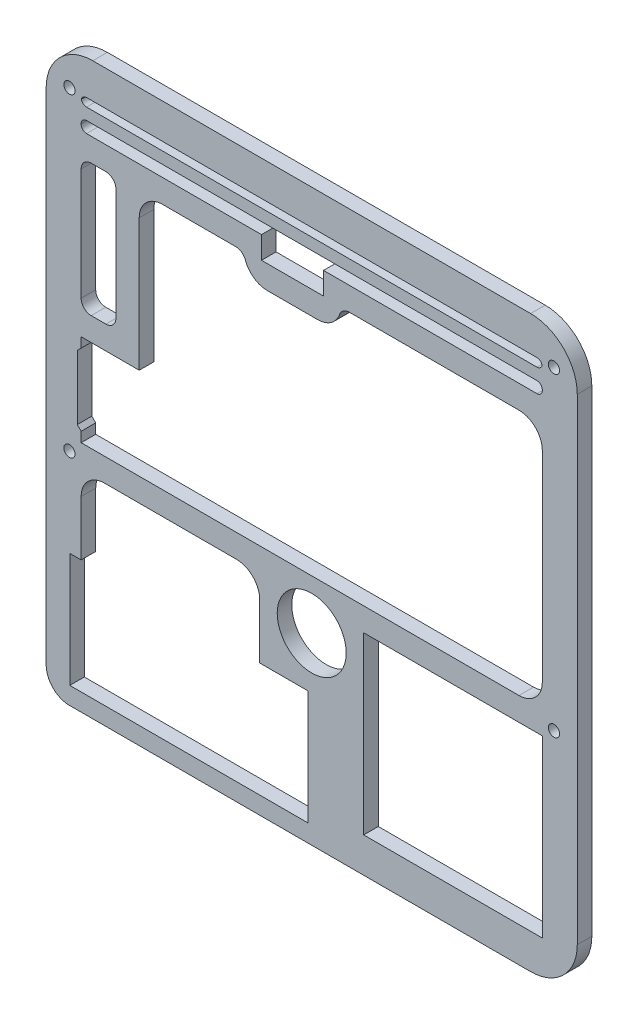
SolidWorks part; units mm, degrees
ref_plane "Front Plane" through (0, 0, 0) normal (0, 0, 1) x (1, 0, 0)
ref_plane "Top Plane" through (0, 0, 0) normal (0, 1, 0) x (1, 0, 0)
ref_plane "Right Plane" through (0, 0, 0) normal (1, 0, 0) x (0, 0, -1)
sketch "Sketch1" plane through (0, 0, 0) normal (0, 0, 1) x (1, 0, 0)
  line L0 (63.9883, 52.5442) -> (63.9883, 48.7342) construction
  line L1 (6.1648, -9.556) -> (64.0322, -9.556)
  line L2 (6.1648, -9.556) -> (6.1648, 52.5442)
  line L3 (6.1648, 52.5442) -> (64.0322, 52.5442)
  line L4 (64.0322, -9.556) -> (64.0322, 52.5442)
  line L5 (60.2222, 48.7342) -> (9.9748, 48.7342)
  line L6 (60.2222, 48.7342) -> (60.2222, -5.746)
  line L7 (60.2222, -5.746) -> (9.9748, -5.746)
  line L8 (9.9748, 48.7342) -> (9.9748, -5.746)
  line L9 (63.9883, 50.6392) -> (18.0707, 50.6392) construction
  line L10 (9.9748, 39.3805) -> (6.1648, 39.3805) construction
  line L11 (8.0698, 39.3805) -> (8.0698, 23.9527) construction
  line L12 (13.5248, -5.746) -> (13.5248, -9.556) construction
  line L13 (13.5248, -7.651) -> (21.1598, -7.651) construction
  line L14 (64.0322, 38.1916) -> (60.2222, 38.1916) construction
  line L15 (62.1272, 38.1916) -> (62.1272, 22.3321) construction
  line L16 (48.6748, 50.6392) -> (23.5288, 50.6392) construction
  line L17 (62.1272, 27.1202) -> (62.1272, 39.363) construction
  line L18 (8.0698, 15.868) -> (8.0698, 3.6252) construction
  line L19 (35.2238, -7.651) -> (34.6952, -7.651) construction
  dimension "D1" = 3.81
  dimension "D2" = 3.81
extrude "Boss-Extrude1" add sketch "Sketch1" along normal blind 1.5875
sketch "Sketch2" plane through (0, 0, 0) normal (0, 0, -1) x (-1, 0, 0)
  line L0 (-60.2222, -5.746) -> (-60.2222, 48.7342) construction
  line L1 (-60.2222, 15.868) -> (-9.9748, 15.868)
  line L2 (-60.2222, 15.868) -> (-60.2222, 13.328)
  line L3 (-60.2222, 13.328) -> (-9.9748, 13.328)
  line L4 (-9.9748, 15.868) -> (-9.9748, 13.328)
  line L5 (-9.9748, 48.7342) -> (-9.9748, -5.746) construction
  line L6 (-13.0532, 15.868) -> (-50.7532, 15.868) construction
  line L7 (-36.3812, 45.3306) -> (-36.3812, 43.2224) construction
  line L8 (-29.6248, 43.2224) -> (-29.6248, 45.3306) construction
  line L9 (-25.4592, 42.9049) -> (-46.8968, 42.9049) construction
  line L11 (-60.2222, 45.3306) -> (-36.3812, 45.3306)
  line L12 (-60.2222, 45.3306) -> (-60.2222, 42.7906)
  line L13 (-60.2222, 42.7906) -> (-38.2862, 42.7906)
  line L14 (-9.9748, 45.3306) -> (-9.9748, 42.7906)
  line L15 (-60.2222, 47.8325) -> (-9.9748, 47.8325)
  line L16 (-60.2222, 47.8325) -> (-60.2222, 46.5625)
  line L17 (-60.2222, 46.5625) -> (-9.9748, 46.5625)
  line L18 (-9.9748, 47.8325) -> (-9.9748, 46.5625)
  line L20 (-55.2788, 45.3306) -> (-16.9248, 45.3306) construction
  line L21 (-55.2788, 46.5625) -> (-16.9248, 46.5625) construction
  line L22 (-36.3812, 42.9049) -> (-36.3812, 45.3306)
  line L23 (-29.6248, 42.9049) -> (-36.3812, 42.9049)
  line L24 (-29.6248, 42.9049) -> (-29.6248, 45.3306)
  line L25 (-38.2862, 42.7906) -> (-38.2862, 40.3649)
  line L26 (-38.2862, 40.3649) -> (-27.7198, 40.3649)
  line L27 (-27.7198, 40.3649) -> (-27.7198, 42.7906)
  line L28 (-27.7198, 42.7906) -> (-9.9748, 42.7906)
  line L29 (-29.6248, 45.3306) -> (-9.9748, 45.3306)
  dimension "D1" = 2.54
  dimension "D2" = 1.905
  dimension "D3" = 2.54
  dimension "D4" = 1.905
  dimension "D5" = 1.27
extrude "Boss-Extrude2" add sketch "Sketch2" against normal up to surface (1.5875 mm away) up to face at (35.0985, 21.4941, 1.5875)
sketch "Sketch3" plane through (0, 0, 0) normal (0, 0, -1) x (-1, 0, 0)
  line L11 (-16.3032, 25.868) -> (-13.0532, 25.868) construction
  line L12 (-16.3032, 25.868) -> (-13.0532, 25.868)
  line L13 (-13.0532, 25.868) -> (-9.9748, 25.868)
  line L14 (-9.9748, 42.7906) -> (-9.9748, 15.868) construction
  line L15 (-9.9748, 25.868) -> (-9.9748, 28.408)
  line L16 (-9.9748, 28.408) -> (-13.7632, 28.408)
  line L17 (-13.7632, 28.408) -> (-13.7632, 42.7906)
  line L18 (-27.7198, 42.7906) -> (-9.9748, 42.7906) construction
  line L19 (-13.7632, 42.7906) -> (-16.3032, 42.7906)
  line L20 (-16.3032, 42.7906) -> (-16.3032, 25.868)
  line L21 (-16.3032, 25.868) -> (-16.2412, 25.8471)
  line M27 (-27.7198, 42.7906) -> (-9.9748, 42.7906)
  line M28 (-9.9748, 42.7906) -> (-9.9748, 15.868)
  dimension "D3" = 2.54
  dimension "D4" = 2.54
extrude "Boss-Extrude3" add sketch "Sketch3" against normal up to surface (1.5875 mm away) contours L20 L12 L13 L16 L17 M27 M28 region at (14.4544, 33.0139, 0) up to face at (35.0985, 48.2834, 1.5875)
sketch "Sketch4" plane through (0, 0, 0) normal (0, 0, -1) x (-1, 0, 0)
  line L0 (-60.2222, 13.328) -> (-9.9748, 13.328) construction
  line L1 (-40.7627, 13.328) -> (-29.4343, 13.328)
  line L2 (-40.7627, 13.328) -> (-40.7627, -5.746)
  line L3 (-40.7627, -5.746) -> (-29.4343, -5.746)
  line L4 (-29.4343, 13.328) -> (-29.4343, -5.746)
  line L5 (-9.9748, -5.746) -> (-60.2222, -5.746) construction
  line L6 (-38.8577, 10.4578) -> (-40.7627, 10.4578) construction
  line L7 (-31.3393, 10.4578) -> (-29.4343, 10.4578) construction
  circle A0 centre (-35.0985, 10.4578) radius 3.7592 construction
  dimension "D1" = 1.905
extrude "Boss-Extrude4" add sketch "Sketch4" against normal up to surface (1.5875 mm away) up to face at (11.869, 35.5993, 1.5875)
sketch "Sketch5" plane through (0, 0, 0) normal (0, 0, -1) x (-1, 0, 0)
  line L0 (-8.7364, 4.8077) -> (-34.6952, 4.8077) construction
  line L3 (-34.6952, -7.651) -> (-34.6952, 4.8077) construction
  line L4 (-8.7364, -7.651) -> (-34.6952, -7.651) construction
  line L5 (-8.7364, -7.651) -> (-8.7364, 4.8077) construction
  line L6 (-8.7364, 4.8077) -> (-34.6952, 4.8077)
  line L7 (-34.6952, -7.651) -> (-34.6952, 4.8077)
  line L8 (-8.7364, -7.651) -> (-34.6952, -7.651)
  line L9 (-8.7364, -7.651) -> (-8.7364, 4.8077)
  circle A0 centre (-35.0985, 10.4578) radius 3.7592 construction
  circle A1 centre (-35.0985, 10.4578) radius 3.7592
extrude "Cut-Extrude1" cut sketch "Sketch5" against normal up to surface (1.5875 mm away) up to face at (50.4924, 3.791, 1.5875)
fillet "Fillet1" radius 5.08 3 edges at (64.0322, -9.556, 0.7937) (6.1648, 52.5442, 0.7937) (64.0322, 52.5442, 0.7937)
fillet "Fillet2" radius 2.54 7 edges at (16.3032, 42.7906, 0.7937) (27.7198, 40.3649, 0.7937) (60.2222, 42.7906, 0.7937) (60.2222, 15.868, 0.7937) (9.9748, 13.328, 0.7937) (29.4343, 13.328, 0.7937) (38.2862, 40.3649, 0.7937)
fillet "Fillet3" radius 1.0922 6 edges at (9.9748, 28.408, 0.7937) (13.7632, 28.408, 0.7937) (9.9748, 42.7906, 0.7937) (13.7632, 42.7906, 0.7937) (27.7198, 42.7906, 0.7937) (38.2862, 42.7906, 0.7937)
fillet "Fillet4" radius 0.5842 8 edges at (9.9748, 45.3306, 0.7937) (9.9748, 47.8325, 0.7937) (9.9748, 48.7342, 0.7937) (9.9748, 46.5625, 0.7937) (60.2222, 47.8325, 0.7937) (60.2222, 48.7342, 0.7937) (60.2222, 46.5625, 0.7937) (60.2222, 45.3306, 0.7937)
fillet "Fillet5" radius 2.54 1 edges at (6.1648, -9.556, 0.7937)
sketch "Sketch6" plane through (0, 0, 0) normal (0, 0, -1) x (-1, 0, 0)
  line L0 (-9.5532, 24.368) -> (-9.5532, 17.368) construction
  line L1 (-9.5532, 24.368) -> (-9.5532, 17.368)
  line L2 (-11.0532, 25.868) -> (-9.5532, 24.368) construction
  line L3 (-11.0532, 25.868) -> (-9.5532, 24.368)
  line L4 (-11.0532, 25.868) -> (-11.0532, 15.868)
  line L6 (-13.0532, 17.368) -> (-13.0532, 15.868)
  line L7 (-13.0532, 15.868) -> (-11.0532, 15.868)
  line L8 (-11.0532, 15.868) -> (-9.5532, 17.368)
  line L9 (-9.5532, 17.368) -> (-13.0532, 17.368)
  line L12 (-11.0532, 15.868) -> (-9.5532, 17.368)
  circle A0 centre (-61.4922, 48.7342) radius 0.6096 construction
  circle A1 centre (-8.7048, 48.7342) radius 0.6096 construction
  circle A2 centre (-61.4922, 14.447) radius 0.6096 construction
  circle A3 centre (-8.7048, 14.447) radius 0.6096 construction
  circle A4 centre (-61.4922, 48.7342) radius 0.6096
  circle A5 centre (-8.7048, 48.7342) radius 0.6096
  circle A6 centre (-61.4922, 14.447) radius 0.6096
  circle A7 centre (-8.7048, 14.447) radius 0.6096
  dimension "D1" = 0
extrude "Cut-Extrude2" cut sketch "Sketch6" against normal up to surface (1.5875 mm away) up to face at (31.3393, 10.4578, 1.5875)
